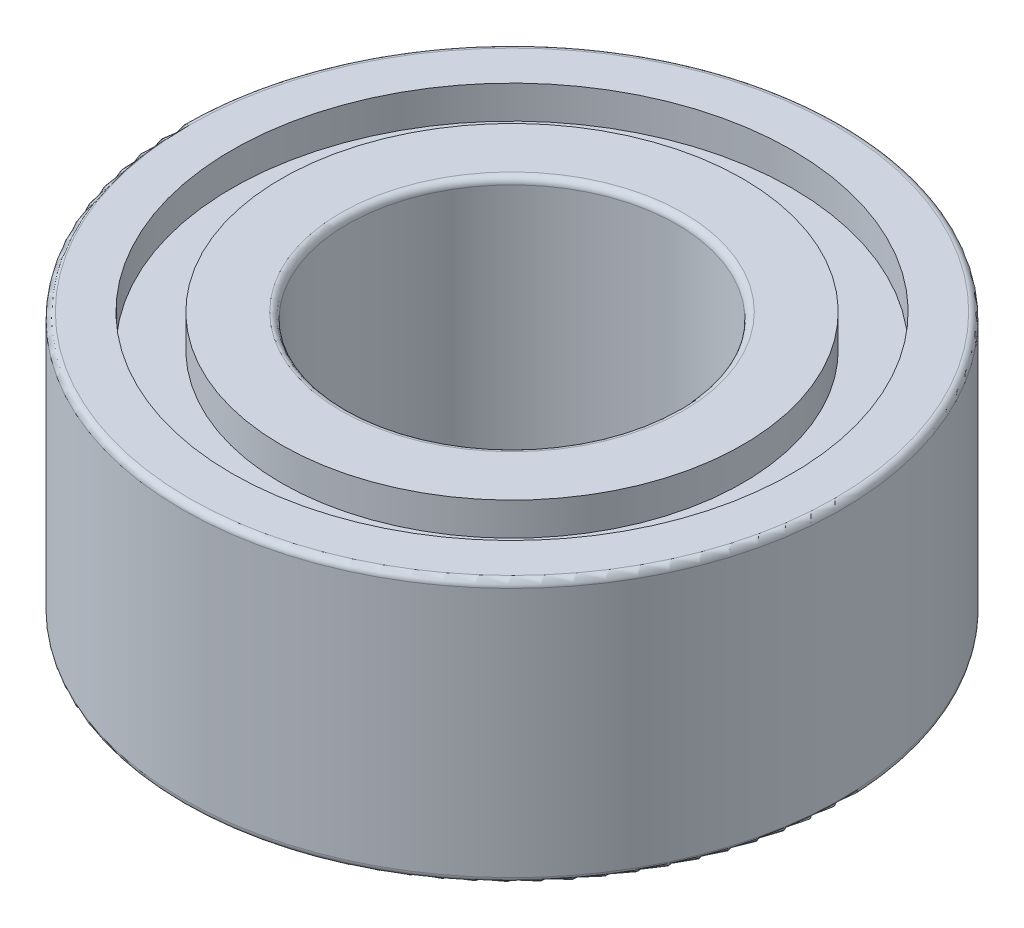
SolidWorks part; units mm, degrees
ref_plane "Front Plane" through (0, 0, 0) normal (0, 0, 1) x (1, 0, 0)
ref_plane "Top Plane" through (0, 0, 0) normal (0, 1, 0) x (1, 0, 0)
ref_plane "Right Plane" through (0, 0, 0) normal (1, 0, 0) x (0, 0, -1)
sketch "Sketch1" plane through (0, 0, 0) normal (0, 1, 0) x (1, 0, 0)
  circle A0 centre (0, 0) radius 5
  circle A1 centre (0, 0) radius 2.5
  dimension "D1" = 10
  dimension "D2" = 5
extrude "Boss-Extrude1" add sketch "Sketch1" along normal blind 2 and the other way blind 2
fillet "Fillet1" radius 0.1 4 edges at (0, -2, 2.5) (0, -2, 5) (0, 2, 5) (0, 2, 2.5)
sketch "Sketch2" plane through (0, 2, 0) normal (0, 1, 0) x (1, 0, 0)
  circle A0 centre (0, 0) radius 4.25
  circle A1 centre (0, 0) radius 3.5
  dimension "D1" = 7
  dimension "D2" = 8.5
extrude "Cut-Extrude1" cut sketch "Sketch2" against normal blind 0.5
mirror "Mirror1" about plane through (0, 0, 0) normal (0, 1, 0) of "Cut-Extrude1"
